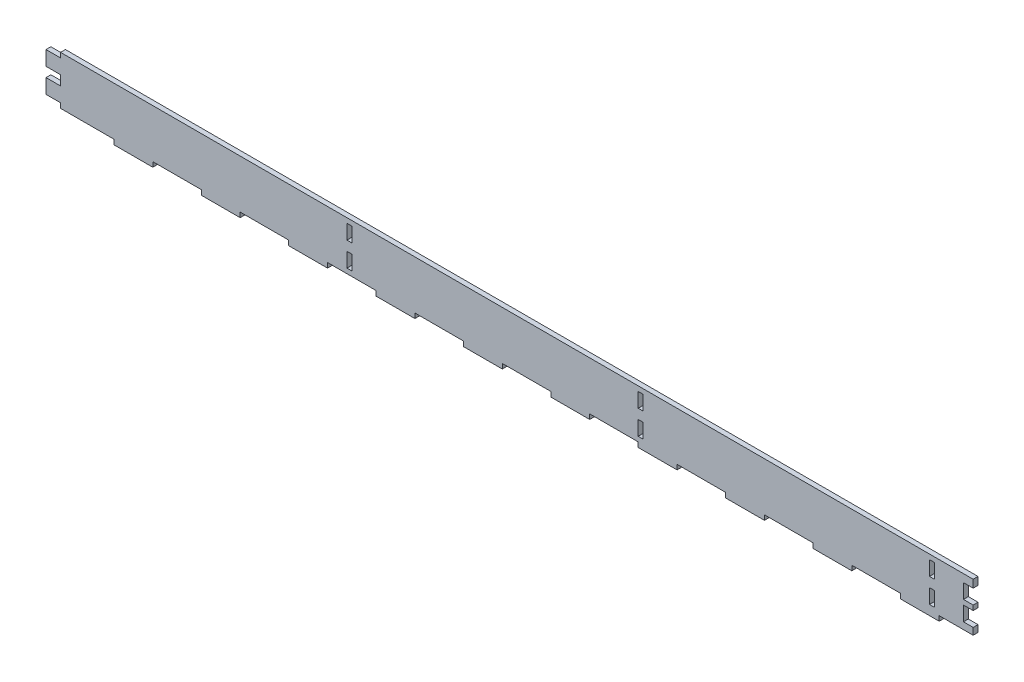
SolidWorks part; units mm, degrees
ref_plane "Front Plane" through (0, 0, 0) normal (0, 0, 1) x (1, 0, 0)
ref_plane "Top Plane" through (0, 0, 0) normal (0, 1, 0) x (1, 0, 0)
ref_plane "Right Plane" through (0, 0, 0) normal (1, 0, 0) x (0, 0, -1)
sketch "Model" plane through (0, 0, 0) normal (0, 0, 1) x (1, 0, 0)
  line L0 (-590, 20) -> (-590, 5)
  line L1 (-590, 5) -> (-585, 5)
  line L2 (-585, 5) -> (-585, 20)
  line L3 (-585, 20) -> (-590, 20)
  line L4 (610, 20) -> (610, 5)
  line L5 (610, 5) -> (615, 5)
  line L6 (615, 5) -> (615, 20)
  line L7 (615, 20) -> (610, 20)
  line L8 (-590, 45) -> (-590, 30)
  line L9 (-590, 30) -> (-585, 30)
  line L10 (-585, 30) -> (-585, 45)
  line L11 (-585, 45) -> (-590, 45)
  line L12 (610, 45) -> (610, 30)
  line L13 (610, 30) -> (615, 30)
  line L14 (615, 30) -> (615, 45)
  line L15 (615, 45) -> (610, 45)
  line L16 (310, 20) -> (310, 5)
  line L17 (310, 5) -> (315, 5)
  line L18 (315, 5) -> (315, 20)
  line L19 (315, 20) -> (310, 20)
  line L20 (310, 45) -> (310, 30)
  line L21 (310, 30) -> (315, 30)
  line L22 (315, 30) -> (315, 45)
  line L23 (315, 45) -> (310, 45)
  line L24 (10, 20) -> (10, 5)
  line L25 (10, 5) -> (15, 5)
  line L26 (15, 5) -> (15, 20)
  line L27 (15, 20) -> (10, 20)
  line L28 (10, 45) -> (10, 30)
  line L29 (10, 30) -> (15, 30)
  line L30 (15, 30) -> (15, 45)
  line L31 (15, 45) -> (10, 45)
  line L32 (-290, 20) -> (-290, 5)
  line L33 (-290, 5) -> (-285, 5)
  line L34 (-285, 5) -> (-285, 20)
  line L35 (-290, 45) -> (-290, 30)
  line L36 (-290, 30) -> (-285, 30)
  line L37 (-285, 30) -> (-285, 45)
  line L38 (-285, 45) -> (-290, 45)
  line L39 (-285, 20) -> (-290, 20)
  line L40 (-885, 0) -> (-830, 0)
  line L41 (-830, 0) -> (-830, -5)
  line L42 (-830, -5) -> (-790, -5)
  line L43 (-790, -5) -> (-790, 0)
  line L44 (-790, 0) -> (-740, 0)
  line L45 (-740, 0) -> (-740, -5)
  line L46 (-740, -5) -> (-700, -5)
  line L47 (-700, -5) -> (-700, 0)
  line L48 (-700, 0) -> (-650, 0)
  line L49 (-650, 0) -> (-650, -5)
  line L50 (-650, -5) -> (-610, -5)
  line L51 (-610, -5) -> (-610, 0)
  line L52 (-610, 0) -> (-560, 0)
  line L53 (-560, 0) -> (-560, -5)
  line L54 (-560, -5) -> (-520, -5)
  line L55 (-520, -5) -> (-520, 0)
  line L56 (-520, 0) -> (-470, 0)
  line L57 (-470, 0) -> (-470, -5)
  line L58 (-470, -5) -> (-430, -5)
  line L59 (-430, -5) -> (-430, 0)
  line L60 (-430, 0) -> (-380, 0)
  line L61 (-380, 0) -> (-380, -5)
  line L62 (-380, -5) -> (-340, -5)
  line L63 (-340, -5) -> (-340, 0)
  line L64 (-340, 0) -> (-290, 0)
  line L65 (-290, 0) -> (-290, -5)
  line L66 (-290, -5) -> (-250, -5)
  line L67 (-250, -5) -> (-250, 0)
  line L68 (-250, 0) -> (-200, 0)
  line L69 (-200, 0) -> (-200, -5)
  line L70 (-200, -5) -> (-160, -5)
  line L71 (-160, -5) -> (-160, 0)
  line L72 (-160, 0) -> (-110, 0)
  line L73 (-110, 0) -> (-110, -5)
  line L74 (-110, -5) -> (-70, -5)
  line L75 (-70, -5) -> (-70, 0)
  line L76 (-70, 0) -> (-20, 0)
  line L77 (-20, 0) -> (-20, -5)
  line L78 (-20, -5) -> (20, -5)
  line L79 (20, -5) -> (20, 0)
  line L80 (20, 0) -> (70, 0)
  line L81 (70, 0) -> (70, -5)
  line L82 (70, -5) -> (110, -5)
  line L83 (110, -5) -> (110, 0)
  line L84 (110, 0) -> (160, 0)
  line L85 (160, 0) -> (160, -5)
  line L86 (160, -5) -> (200, -5)
  line L87 (200, -5) -> (200, 0)
  line L88 (200, 0) -> (250, 0)
  line L89 (250, 0) -> (250, -5)
  line L90 (250, -5) -> (290, -5)
  line L91 (290, -5) -> (290, 0)
  line L92 (290, 0) -> (340, 0)
  line L93 (340, 0) -> (340, -5)
  line L94 (340, -5) -> (380, -5)
  line L95 (380, -5) -> (380, 0)
  line L96 (380, 0) -> (430, 0)
  line L97 (430, 0) -> (430, -5)
  line L98 (430, -5) -> (470, -5)
  line L99 (470, -5) -> (470, 0)
  line L100 (470, 0) -> (520, 0)
  line L101 (520, 0) -> (520, -5)
  line L102 (520, -5) -> (560, -5)
  line L103 (560, -5) -> (560, 0)
  line L104 (560, 0) -> (610, 0)
  line L105 (610, 0) -> (610, -5)
  line L106 (610, -5) -> (650, -5)
  line L107 (650, -5) -> (650, 0)
  line L108 (650, 0) -> (700, 0)
  line L109 (700, 0) -> (700, -5)
  line L110 (700, -5) -> (740, -5)
  line L111 (740, -5) -> (740, 0)
  line L112 (740, 0) -> (790, 0)
  line L113 (790, 0) -> (790, -5)
  line L114 (790, -5) -> (830, -5)
  line L115 (830, -5) -> (830, 0)
  line L116 (830, 0) -> (885, 0)
  line L117 (885, 0) -> (885, 5)
  line L118 (885, 5) -> (900, 5)
  line L119 (900, 5) -> (900, 20)
  line L120 (900, 20) -> (885, 20)
  line L121 (885, 20) -> (885, 30)
  line L122 (885, 30) -> (900, 30)
  line L123 (900, 30) -> (900, 45)
  line L124 (900, 45) -> (885, 45)
  line L125 (885, 45) -> (885, 50)
  line L126 (885, 50) -> (-885, 50)
  line L127 (-885, 50) -> (-885, 45)
  line L128 (-885, 45) -> (-900, 45)
  line L129 (-900, 45) -> (-900, 30)
  line L130 (-900, 30) -> (-885, 30)
  line L131 (-885, 30) -> (-885, 20)
  line L132 (-885, 20) -> (-900, 20)
  line L133 (-900, 20) -> (-900, 5)
  line L134 (-900, 5) -> (-885, 5)
  line L135 (-885, 5) -> (-885, 0)
extrude "Boss-Extrude1" add sketch "Model" along normal blind 5
sketch "Sketch1" plane through (0, 0, 5) normal (0, 0, 1) x (1, 0, 0)
  line L0 (55, 50) -> (55, 42)
  line L1 (885, 50) -> (-885, 50) construction
  line L2 (55, 42) -> (45, 42)
  line L3 (45, 42) -> (45, 27)
  line L4 (45, 27) -> (55, 27)
  line L5 (55, 27) -> (55, 22)
  line L6 (55, 22) -> (45, 22)
  line L7 (45, 22) -> (45, 7)
  line L8 (45, 7) -> (55, 7)
  line L9 (55, 7) -> (55, 0)
  line L10 (20, 0) -> (70, 0) construction
  line L11 (55, 50) -> (1126.3018, 127.7544)
  line L12 (1126.3018, 127.7544) -> (770.7619, -361.9579)
  line L13 (770.7619, -361.9579) -> (55, 0)
  point P12 (770.7619, -361.9579)
  dimension "D1" = 5
  dimension "D2" = 10
  dimension "D3" = 10
  dimension "D4" = 10
  dimension "D5" = 10
  dimension "D6" = 8
  dimension "D7" = 15
  dimension "D8" = 15
  dimension "D9" = 35
extrude "Cut-Extrude1" cut sketch "Sketch1" against normal through all
